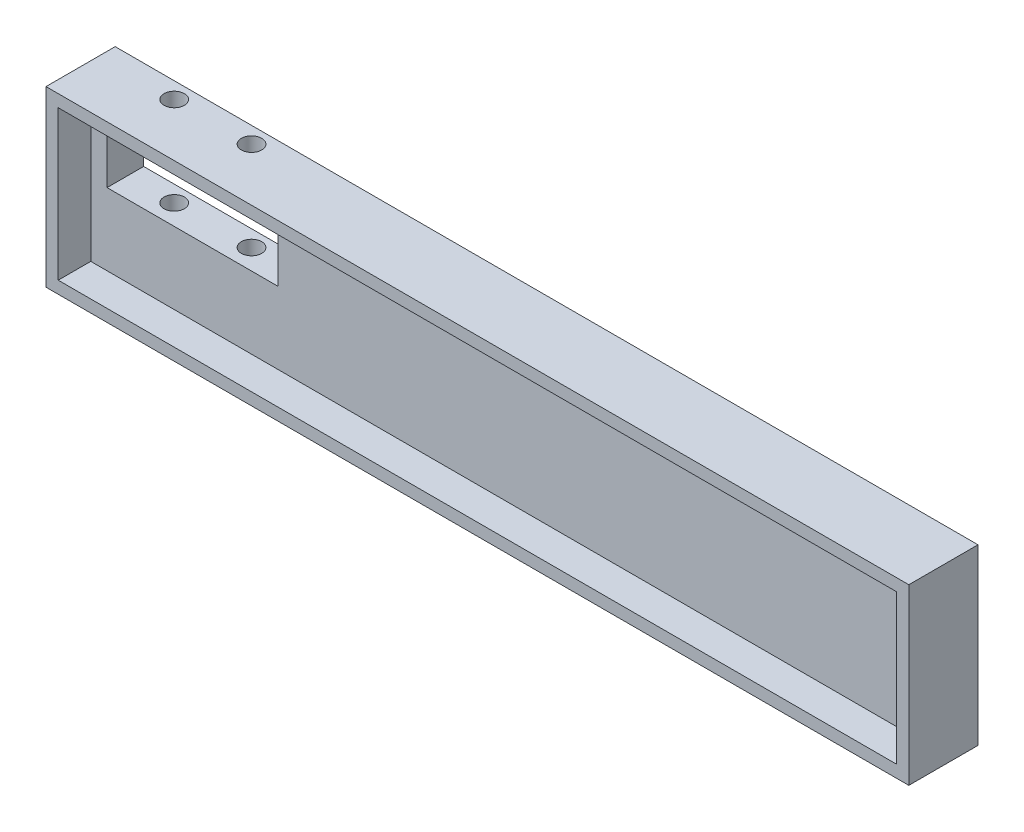
SolidWorks part; units mm, degrees
ref_plane "Plano frontal" through (0, 0, 0) normal (0, 0, 1) x (1, 0, 0)
ref_plane "Plano superior" through (0, 0, 0) normal (0, 1, 0) x (1, 0, 0)
ref_plane "Plano direito" through (0, 0, 0) normal (1, 0, 0) x (0, 0, -1)
sketch "Esboço1" plane through (0, 0, 0) normal (0, 0, 1) x (1, 0, 0)
  line L0 (-5.5, 16.8911) -> (-5.5, 9.3884)
  line L1 (-5.5, 16.8911) -> (87.5, 16.8911)
  line L2 (-5.5, 16.8911) -> (-5.5, -1.4589)
  line L3 (-5.5, -1.4589) -> (87.5, -1.4589)
  line L4 (99, -2.9589) -> (86, -2.9589)
  line L5 (99, 18.3911) -> (99, -2.9589)
  line L6 (99, 18.3911) -> (86, 18.3911)
  line L7 (-5, -0.9589) -> (88, -0.9589)
  line L8 (-5, -0.9589) -> (-5, 16.3911)
  line L9 (-5, 16.3911) -> (88, 16.3911)
  line L10 (97, 16.3911) -> (88, 16.3911)
  line L11 (97, -0.9589) -> (97, 16.3911)
  line L12 (97, -0.9589) -> (88, -0.9589)
  line L13 (-7, 18.3911) -> (86, 18.3911)
  line L14 (-7, 18.3911) -> (-7, -2.9589)
  line L15 (-7, -2.9589) -> (86, -2.9589)
  line L16 (97.5, -1.4589) -> (87.5, -1.4589)
  line L17 (97.5, 16.8911) -> (97.5, -1.4589)
  line L18 (97.5, 16.8911) -> (87.5, 16.8911)
  line L20 (17.5, 9.3884) -> (17.5, 14.8911)
  line L21 (17.5, 16.8911) -> (-5.5, 16.8911)
  line L22 (-5.5, 16.8911) -> (-3.5, 16.8911)
  line L24 (-3.5, 14.8911) -> (17.5, 14.8911)
  line L25 (-3.5, 14.8911) -> (-3.5, 7.3911)
  line L26 (-3.5, 7.3911) -> (17.5, 7.3911)
  line L27 (17.5, 7.3911) -> (17.5, 9.3884)
  dimension "D1" = 2
  dimension "D2" = 21
  dimension "D3" = 2
  dimension "D4" = 2
  dimension "D5" = 7.5
  dimension "D6" = 0.5
  dimension "D7" = 0.5
  dimension "D8" = 13
  dimension "D9" = 10
  dimension "D10" = 9
extrude "Ressalto-extrusão1" add sketch "Esboço1" along normal blind 5 contours L13 L14 L15 L1 L3 L2 region at (92.5, -1.8776, 0)
extrude "Ressalto-extrusão2" add sketch "Esboço1<4>" against normal blind 3.5 contours L13 L14 L15 L1 L3 L2 | L1 L2 L3 L7 L8 L9 | L7 L9 L8 region at (-4.5, 16.7865, 0) region at (92.5, -1.8776, 0) region at (49.81, 7.3815, 0)
sketch "Esboço1<4>" plane through (0, 0, 0) normal (0, 0, 1) x (1, 0, 0) same geometry as "Esboço1"
sketch "Esboço3" plane through (0, 0, 0) normal (0, 1, 0) x (1, 0, 0)
  line L0 (-7, 3.5) -> (-7, 0)
  line L1 (-7, -5) -> (-7, 3.5) construction
  circle A0 centre (2.25, 1.5) radius 1.25
  circle A1 centre (11.75, 1.5) radius 1.25
  dimension "D1" = 3.5
  dimension "D2" = 1.5
  dimension "D3" = 1.5
  dimension "D4" = 9.25
  dimension "D5" = 9.5
extrude "Corte-extrusão10" cut sketch "Esboço3" along normal blind 30 from surface contours A0 | A1 starting at face at (46, -2.9589, 0.75)
extrude "Ressalto-extrusão4" add sketch "Esboço1<7>" along normal blind 1 contours L17 L18 L1 L21 L0 L2 L3 L16 L11 L12 L7 L8 L9 L10 | L12 L11 L10 L9 L8 L7 L27 L26 L25 L24 L20 region at (-4.5, 16.7865, 0) region at (49.81, 7.3815, 0)
sketch "Esboço1<7>" plane through (0, 0, 0) normal (0, 0, 1) x (1, 0, 0) same geometry as "Esboço1"
